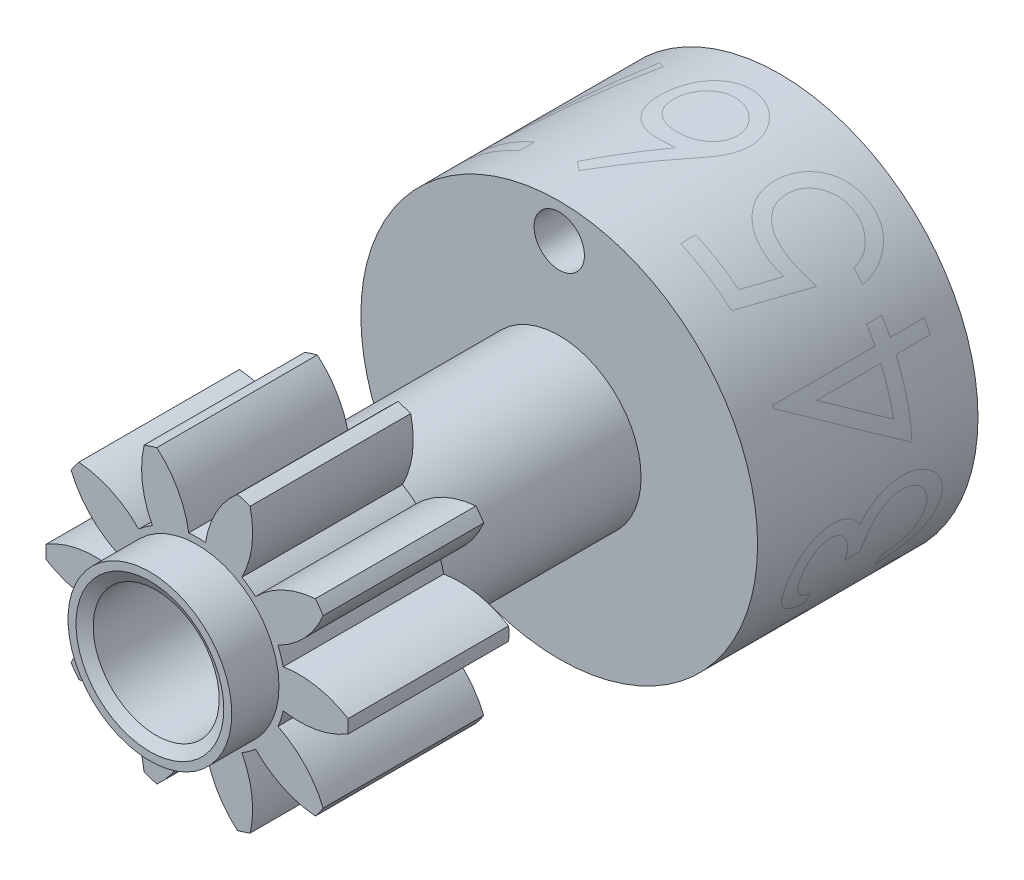
SolidWorks part; units mm, degrees
ref_plane "Front Plane" through (0, 0, 0) normal (0, 0, 1) x (1, 0, 0)
ref_plane "Top Plane" through (0, 0, 0) normal (0, 1, 0) x (1, 0, 0)
ref_plane "Right Plane" through (0, 0, 0) normal (1, 0, 0) x (0, 0, -1)
sketch "Sketch1" plane through (0, 0, 0) normal (0, 0, 1) x (1, 0, 0)
  circle A0 centre (0, 0) radius 1.3
  dimension "D1" = 2.6
extrude "Boss-Extrude1" add sketch "Sketch1" against normal blind 10
sketch "Sketch2" plane through (0, 0, -10) normal (0, 0, -1) x (-1, 0, 0)
  circle A0 centre (0, 0) radius 3.15
  dimension "D1" = 6.3
extrude "Boss-Extrude2" add sketch "Sketch2" against normal offset from surface (3.5 mm away) 6.5 up to face at (1.3, 0, 0)
sketch "Sketch3" plane through (0, 0, -10) normal (0, 0, -1) x (-1, 0, 0)
  circle A0 centre (0, 0) radius 1.75
  dimension "D1" = 3.5
extrude "Boss-Extrude3" add sketch "Sketch3" along normal offset from surface (0.2 mm away) 10.2 up to face at (1.3, 0, 0)
sketch "Sketch4" plane through (0, 0, 0) normal (1, 0, 0) x (0, 0, -1)
  line L0 (0, 0) -> (10.2, 0) construction
  line L1 (10.2, -1.75) -> (10.2, 1.75) construction
  line L2 (0, 1.3) -> (0, -1.3) construction
  line L4 (3.3, -1.3) -> (3.3, -2.4)
  line L7 (0, -1.3) -> (6.5, -1.3) construction
  line L9 (0.75, -1.3) -> (3.3, -1.3)
  line L10 (0.75, -1.3) -> (0.75, -2.4)
  line L11 (0.75, -2.4) -> (3.3, -2.4)
  dimension "D1" = 3.3
  dimension "D2" = 4.8
  dimension "D4" = 0.75
revolve "Revolve1" add sketch "Sketch4" angle 360 about L0
sketch "Sketch5" plane through (0, 0, 0) normal (0, 0, 1) x (1, 0, 0)
  circle A0 centre (0, 0) radius 1
  dimension "D1" = 2
extrude "Cut-Extrude1" cut sketch "Sketch5" against normal through all
chamfer "Chamfer1" distance 0.1 angle 45 1 edges at (1.75, 0, -10.2)
sketch "Sketch6" plane through (0, 0, 0) normal (1, 0, 0) x (0, 0, -1)
  line L0 (0, 0) -> (10.2, 0) construction
  line L1 (10.2, -1.65) -> (10.2, 1.65) construction
  line L2 (10.2, 1.4) -> (7.7751, 0)
  line L3 (7.7751, 0) -> (10.2, 0)
  line L4 (10.2, 0) -> (10.2, 1.4)
  dimension "D1" = 30
  dimension "D2" = 2.8
revolve "Cut-Revolve1" cut sketch "Sketch6" angle 360 about L0
chamfer "Chamfer2" distance 0.1 angle 60 1 edges at (1, 0, 0) first distance on face at (1, 0, 0)
sketch "Sketch7" plane through (0, 0, -6.5) normal (0, 0, 1) x (1, 0, 0)
  line L0 (0, 0) -> (0, 3.15) construction
  circle A0 centre (0, 2.6) radius 0.4
  circle A1 centre (0, 0) radius 3.15 construction
  dimension "D1" = 0.8
  dimension "D2" = 2.6
extrude "Cut-Extrude2" cut sketch "Sketch7" against normal up to next
sketch "Sketch8" plane through (0, 0, -0.75) normal (0, 0, 1) x (1, 0, 0)
  line L0 (0, 0) -> (0, 2.4) construction
  line L1 (0, 0) -> (-0.618, 1.9021) construction
  line L2 (0, 0) -> (0.618, 1.9021) construction
  line L3 (0, 0) -> (-2.4, 0) construction
  line L4 (0, 0) -> (-1.618, -1.1756) construction
  circle A0 centre (0, 0) radius 2.4 construction
  circle A1 centre (0, 0) radius 2 construction
  arc A2 (0.6402, -2.313) -> (0.134, -1.3936) centre (1.618, -1.1756) cw
  arc A3 (-0.134, -1.3936) -> (0.134, -1.3936) centre (0, 0) ccw
  arc A4 (-0.6402, -2.313) -> (-0.134, -1.3936) centre (-1.618, -1.1756) ccw
  arc A5 (-0.6402, -2.313) -> (0.6402, -2.313) centre (0, 0) ccw
  dimension "D1" = 4
  dimension "D4" = 2.8
  dimension "D6" = 3
  dimension "D2" = 18
  dimension "D3" = 18
  dimension "D5" = 36
extrude "Cut-Extrude3" cut sketch "Sketch8" against normal up to next
pattern_circular "CirPattern1" count 10 over 360 about axis through (0, 0, -10.2) along (0, 0, 1) of "Cut-Extrude3"
sketch "Sketch10" plane through (0, 0, -0.75) normal (0, 0, 1) x (1, 0, 0)
  line L0 (0, 0) -> (1.6068, 2.2116) construction
  circle A0 centre (0, 0) radius 1.9874 construction
  circle A1 centre (1.6068, 2.2116) radius 0.7463
  arc A2 (0.7107, 1.2062) -> (0.8416, 2.2476) centre (-0.618, 1.9021) ccw construction
  arc A3 (1.8775, 1.495) -> (0.9275, 1.0487) centre (2, 0) ccw construction
  dimension "D1" = 3.48
sketch "Sketch11" plane through (0, 0, -3.3) normal (0, 0, -1) x (-1, 0, 0)
  line L0 (0, 0) -> (5.1563, -7.097) construction
  line L1 (0, 0) -> (-3.15, 0) construction
  circle A0 centre (0, 0) radius 3.15 construction
  circle A1 centre (3.703, -5.0968) radius 5
  point P9 (0.7641, -1.0517)
  dimension "D2" = 10
  dimension "D1" = 54
  dimension "D3" = 1.3
extrude "Cut-Extrude4" cut sketch "Sketch11" against normal offset from surface (0.9 mm away) 2.4 contours A1 up to face at (1.1732, 0, 0)
sketch "Sketch12" plane through (0, 0, -10) normal (0, 0, -1) x (-1, 0, 0)
  line L0 (0, 0) -> (0, 3.15) construction
  line L1 (0, 0) -> (1.8515, 2.5484) construction
  line L2 (0, 0) -> (2.9958, 0.9734) construction
  line L3 (0, 0) -> (2.9958, -0.9734) construction
  line L4 (0, 0) -> (1.8515, -2.5484) construction
  line L5 (0, 0) -> (0, -3.15) construction
  line L6 (0, 0) -> (-1.8515, -2.5484) construction
  line L7 (0, 0) -> (-2.9958, -0.9734) construction
  line L8 (0, 0) -> (-2.9958, 0.9734) construction
  line L9 (0, 0) -> (-1.8515, 2.5484) construction
  circle A0 centre (0, 0) radius 3.15 construction
  point P17 (0, 0)
  dimension "D1" = 10
ref_plane "Plane2" through (0, 3.15, -10) normal (0, 1, 0) x (1, 0, 0)
sketch "Sketch14" plane through (0, 3.15, -10) normal (0, 1, 0) x (1, 0, 0)
  line L0 (0, 0) -> (0, -3.5) construction
  line L1 (-0.675, -0.5) -> (0.675, -0.5)
  line L2 (-0.675, -0.5) -> (-0.675, -2.85)
  line L3 (-0.675, -2.85) -> (0.675, -2.85)
  line L4 (0.675, -0.5) -> (0.675, -2.85)
  line L5 (-3.15, -3.5) -> (3.15, -3.5) construction
  line L6 (0, 0) -> (1.8515, 0) construction
  line L7 (-2.5, -0.5) -> (2.5, -0.5)
  dimension "D1" = 0.5
  dimension "D2" = 2.35
  dimension "D3" = 1.35
  dimension "D4" = 5
sketch "Sketch20" plane through (0, 3.15, -10) normal (0, 1, 0) x (1, 0, 0)
  text T0 "6" font "Century Gothic" height 2.35
wrap "Wrap2" sketch "Sketch20" wrap type scribe source sketch "Sketch20" face at (-3.15, 0, -10)
ref_plane "Plane3" through (1.8515, 2.5484, -10) normal (0.5878, 0.809, 0) x (0.809, -0.5878, 0)
sketch "Sketch21" plane through (1.8515, 2.5484, -10) normal (0.5878, 0.809, 0) x (0.809, -0.5878, 0)
  line L0 (0, 0) -> (0, -3.5) construction
  line L1 (-1.3, -3.5) -> (1.3, -3.5) construction
  line L3 (-1, -0.5) -> (1, -0.5) construction
  line L4 (0, 0) -> (1.8515, 0) construction
  text T0 "5" font "Century Gothic" height 2.35
  dimension "D1" = 2
  dimension "D2" = 0.5
wrap "Wrap3" sketch "Sketch21" wrap type scribe source sketch "Sketch21" face at (-3.15, 0, -10)
ref_plane "Plane4" through (2.9958, 0.9734, -10) normal (0.9511, 0.309, 0) x (0, 0, -1)
sketch "Sketch22" plane through (2.9958, 0.9734, -10) normal (0.9511, 0.309, 0) x (0, 0, -1)
  line L0 (0, 0) -> (-3.5, 0) construction
  line L1 (-3.5, 3.15) -> (-3.5, -3.15) construction
  line L2 (-0.5, 1) -> (-0.5, -1) construction
  line L3 (0, 0) -> (0, -1.8515) construction
  text T0 "4" font "Century Gothic" height 2.35
  dimension "D1" = 2
  dimension "D2" = 0.5
wrap "Wrap4" sketch "Sketch22" wrap type scribe source sketch "Sketch22" face at (1.8301, 2.528, -8.2739)
ref_plane "Plane5" through (2.9958, -0.9734, -10) normal (0.9511, -0.309, 0) x (0, 0, -1)
sketch "Sketch24" plane through (2.9958, -0.9734, -10) normal (0.9511, -0.309, 0) x (0, 0, -1)
  line L0 (0, 0) -> (-3.5, 0) construction
  line L1 (-3.5, 3.15) -> (-3.5, -3.15) construction
  line L2 (-0.5, 1) -> (-0.5, -1) construction
  line L3 (0, 0) -> (0, -1.8515) construction
  text T0 "3" font "Century Gothic" height 2.35
  dimension "D1" = 0.5
  dimension "D2" = 2
wrap "Wrap5" sketch "Sketch24" wrap type scribe source sketch "Sketch24" face at (1.8301, 2.528, -8.2739)
ref_plane "Plane6" through (1.8515, -2.5484, -10) normal (0.5878, -0.809, 0) x (-0.809, -0.5878, 0)
sketch "Sketch25" plane through (1.8515, -2.5484, -10) normal (0.5878, -0.809, 0) x (-0.809, -0.5878, 0)
  line L0 (0, 0) -> (0, -3.5) construction
  line L1 (-3.15, -3.5) -> (3.15, -3.5) construction
  line L2 (-1, -0.5) -> (1, -0.5) construction
  line L3 (0, 0) -> (1.8515, 0) construction
  text T0 "2" font "Century Gothic" height 2.35
  point P8 (0, -0.5)
  dimension "D1" = 2
  dimension "D2" = 0.5
wrap "Wrap6" sketch "Sketch25" wrap type scribe source sketch "Sketch25" face at (1.8301, 2.528, -8.2739)
ref_plane "Plane7" through (0, -3.15, -10) normal (0, -1, 0) x (-1, 0, 0)
sketch "Sketch26" plane through (0, -3.15, -10) normal (0, -1, 0) x (-1, 0, 0)
  line L0 (0, 0) -> (0, -3.5) construction
  line L1 (-3.15, -3.5) -> (3.15, -3.5) construction
  line L2 (-1, -0.5) -> (1, -0.5) construction
  line L3 (0, 0) -> (1.8515, 0) construction
  text T0 "1" font "Century Gothic" height 2.35
  point P8 (0, -0.5)
  dimension "D1" = 2
  dimension "D2" = 0.5
wrap "Wrap7" sketch "Sketch26" wrap type scribe source sketch "Sketch26" face at (1.8301, 2.528, -8.2739)
ref_plane "Plane8" through (-1.8515, -2.5484, -10) normal (-0.5878, -0.809, 0) x (-0.809, 0.5878, 0)
sketch "Sketch27" plane through (-1.8515, -2.5484, -10) normal (-0.5878, -0.809, 0) x (-0.809, 0.5878, 0)
  line L0 (0, 0) -> (0, -3.5) construction
  line L1 (-3.15, -3.5) -> (3.15, -3.5) construction
  line L2 (-1, -0.5) -> (1, -0.5) construction
  line L3 (0, 0) -> (1.8515, 0) construction
  text T0 "0" font "Century Gothic" height 2.35
  point P8 (0, -0.5)
  dimension "D1" = 0.5
  dimension "D2" = 2
wrap "Wrap8" sketch "Sketch27" wrap type scribe source sketch "Sketch27" face at (1.8301, 2.528, -8.2739)
ref_plane "Plane9" through (-2.9958, -0.9734, -10) normal (-0.9511, -0.309, 0) x (0, 0, 1)
sketch "Sketch28" plane through (-2.9958, -0.9734, -10) normal (-0.9511, -0.309, 0) x (0, 0, 1)
  line L0 (0, 0) -> (3.5, 0) construction
  line L1 (3.5, -3.15) -> (3.5, 3.15) construction
  line L2 (0.5, -1) -> (0.5, 1) construction
  line L3 (0, 0) -> (0, 1.8515) construction
  text T0 "9" font "Century Gothic" height 2.35
  point P8 (0.5, 0)
  dimension "D1" = 2
  dimension "D2" = 0.5
wrap "Wrap9" sketch "Sketch28" wrap type scribe source sketch "Sketch28" face at (-1.8048, -2.5201, -8.3255)
ref_plane "Plane10" through (-2.9958, 0.9734, -10) normal (-0.9511, 0.309, 0) x (0, 0, 1)
sketch "Sketch29" plane through (-2.9958, 0.9734, -10) normal (-0.9511, 0.309, 0) x (0, 0, 1)
  line L0 (0, 0) -> (3.5, 0) construction
  line L1 (3.5, -3.15) -> (3.5, 3.15) construction
  line L2 (0.5, -1) -> (0.5, 1) construction
  line L3 (0, 0) -> (0, -1.8515) construction
  text T0 "8" font "Century Gothic" height 2.35
  point P8 (0.5, 0)
  dimension "D1" = 0.5
  dimension "D2" = 2
wrap "Wrap10" sketch "Sketch29" wrap type scribe source sketch "Sketch29" face at (-1.8048, -2.5201, -8.3255)
ref_plane "Plane11" through (-1.8515, 2.5484, -10) normal (-0.5878, 0.809, 0) x (0.809, 0.5878, 0)
sketch "Sketch30" plane through (-1.8515, 2.5484, -10) normal (-0.5878, 0.809, 0) x (0.809, 0.5878, 0)
  line L0 (0, 0) -> (0, -3.5) construction
  line L1 (-3.15, -3.5) -> (3.15, -3.5) construction
  line L2 (-1, -0.5) -> (1, -0.5) construction
  line L4 (0, 0) -> (2.9958, 0) construction
  text T0 "7" font "Century Gothic" height 2.35
  point P9 (0, -0.5)
  dimension "D1" = 2
  dimension "D2" = 0.5
wrap "Wrap11" sketch "Sketch30" wrap type scribe source sketch "Sketch30" face at (-1.8048, -2.5201, -8.3255)
